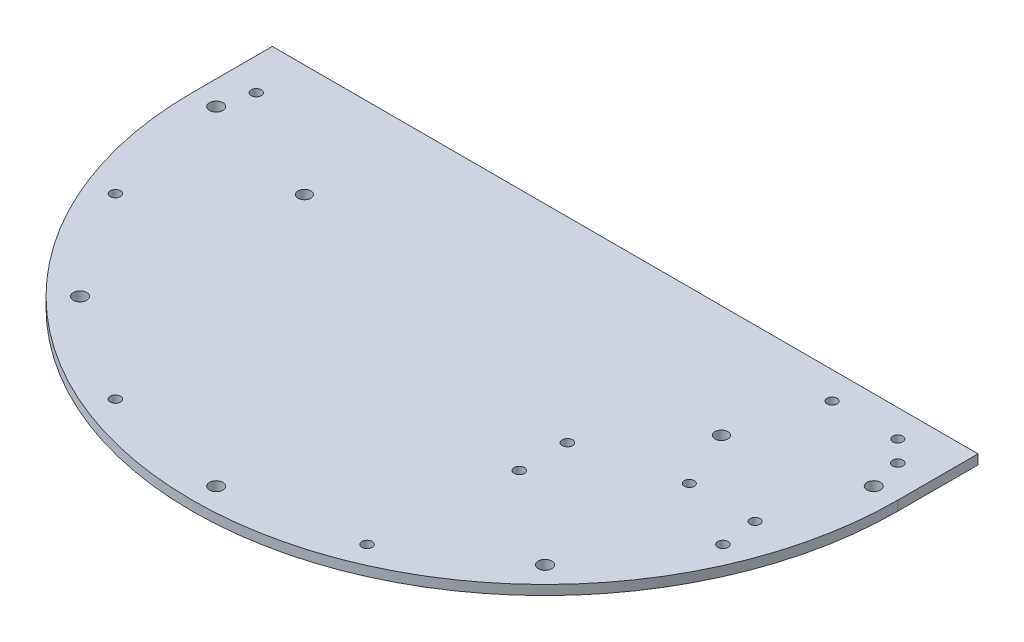
SolidWorks part; units mm, degrees
ref_plane "前视基准面" through (0, 0, 0) normal (0, 0, 1) x (1, 0, 0)
ref_plane "上视基准面" through (0, 0, 0) normal (0, 1, 0) x (1, 0, 0)
ref_plane "右视基准面" through (0, 0, 0) normal (1, 0, 0) x (0, 0, -1)
sketch "草图1" plane through (0, 0, 0) normal (0, 1, 0) x (1, 0, 0)
  line L0 (0, 0) -> (-173.2727, 0) construction
  line L2 (-110, 0) -> (-110, 125)
  line L3 (-110, 125) -> (110, 125)
  line L4 (110, 0) -> (110, 125)
  arc A0 (-110, 0) -> (110, 0) centre (0, 0) ccw
  point P0 (0, 0)
  dimension "D3" = 125
  dimension "D1" = 220
extrude "凸台-拉伸1" add sketch "草图1" along normal blind 3 contours L4 L3 L2 A0
sketch "草图2" plane through (0, 3, 0) normal (0, 1, 0) x (1, 0, 0)
  line L0 (-110, 125) -> (110, 125) construction
  line L1 (-110, 225) -> (110, 225)
  line L2 (-110, 225) -> (-110, 25)
  line L3 (-110, 25) -> (110, 25)
  line L4 (110, 225) -> (110, 25)
  line L5 (-110, 225) -> (110, 25) construction
  line L6 (-110, 25) -> (110, 225) construction
  line L8 (110, 0) -> (110, 125) construction
  point P0 (0, 125)
  dimension "D1" = 100
extrude "切除-拉伸1" cut sketch "草图2" against normal through all
sketch "草图3" plane through (0, 3, 0) normal (0, 1, 0) x (1, 0, 0)
  line L0 (0, 0) -> (0, 64.3279) construction
  line L1 (-110, 25) -> (110, 25) construction
  line L2 (0, 0) -> (-186.1091, 0) construction
  line L3 (-117.1533, -10) -> (119.4118, -10) construction
  line L4 (0, 0) -> (-94.6977, -39.2251) construction
  circle A0 centre (-65, -10) radius 2
  circle A1 centre (65, -10) radius 2
  arc A2 (-102.5, 0) -> (102.5, 0) centre (0, 0) ccw construction
  circle A3 centre (0, -102.5) radius 2.1
  circle A4 centre (-72.4784, -72.4784) radius 2.1
  circle A5 centre (-102.5, 0) radius 2.1
  circle A9 centre (102.5, 0) radius 2.1
  circle A10 centre (72.4784, -72.4784) radius 2.1
  circle A11 centre (-72.4784, 72.4784) radius 2.1 [skipped]
  circle A12 centre (0, 102.5) radius 2.1 [skipped]
  circle A13 centre (72.4784, 72.4784) radius 2.1 [skipped]
  circle A14 centre (-94.6977, -39.2251) radius 1.6
  circle A19 centre (94.6977, -39.2251) radius 1.6
  circle A20 centre (39.2251, -94.6977) radius 1.6
  circle A21 centre (-39.2251, -94.6977) radius 1.6
  circle A22 centre (-94.6977, 39.2251) radius 1.6 [skipped]
  circle A23 centre (-39.2251, 94.6977) radius 1.6 [skipped]
  circle A24 centre (39.2251, 94.6977) radius 1.6 [skipped]
  circle A25 centre (94.6977, 39.2251) radius 1.6 [skipped]
  dimension "D1" = 4
  dimension "D4" = 205
  dimension "D5" = 10
  dimension "D6" = 4.2
  dimension "D8" = 3.2
  dimension "D2" = 65
  dimension "D3" = 35
  dimension "D9" = 22.5
  dimension "D7" = 8
  dimension "D10" = 8
extrude "切除-拉伸2" cut sketch "草图3" against normal blind 10
sketch "草图4" plane through (0, 3, 0) normal (0, 1, 0) x (1, 0, 0)
  line L0 (0, 0) -> (0, -38.258) construction
  circle A0 centre (-100, 10) radius 1.6
  circle A1 centre (-102.5, 0) radius 2.1 construction
  circle A2 centre (100, 10) radius 1.6
  circle A3 centre (43, -36) radius 1.6
  circle A4 centre (43, -51) radius 1.6
  circle A5 centre (73, -28) radius 1.55
  circle A6 centre (93.5, -28) radius 1.55
  circle A7 centre (93.5, 16.5) radius 1.55
  circle A8 centre (73, 16.5) radius 1.55
  dimension "D1" = 3.2
  dimension "D4" = 3.2
  dimension "D9" = 3.1
  dimension "D2" = 10
  dimension "D3" = 2.5
  dimension "D5" = 43
  dimension "D6" = 36
  dimension "D8" = 15
  dimension "D12" = 73
  dimension "D13" = 28
  dimension "D7" = 2
  dimension "D10" = 2
  dimension "D11" = 2
extrude "切除-拉伸3" cut sketch "草图4" against normal through all contours A0 | A2
extrude "切除-拉伸4" cut sketch "草图4<3>" against normal blind 10
sketch "草图4<3>" plane through (0, 3, 0) normal (0, 1, 0) x (1, 0, 0) same geometry as "草图4"
